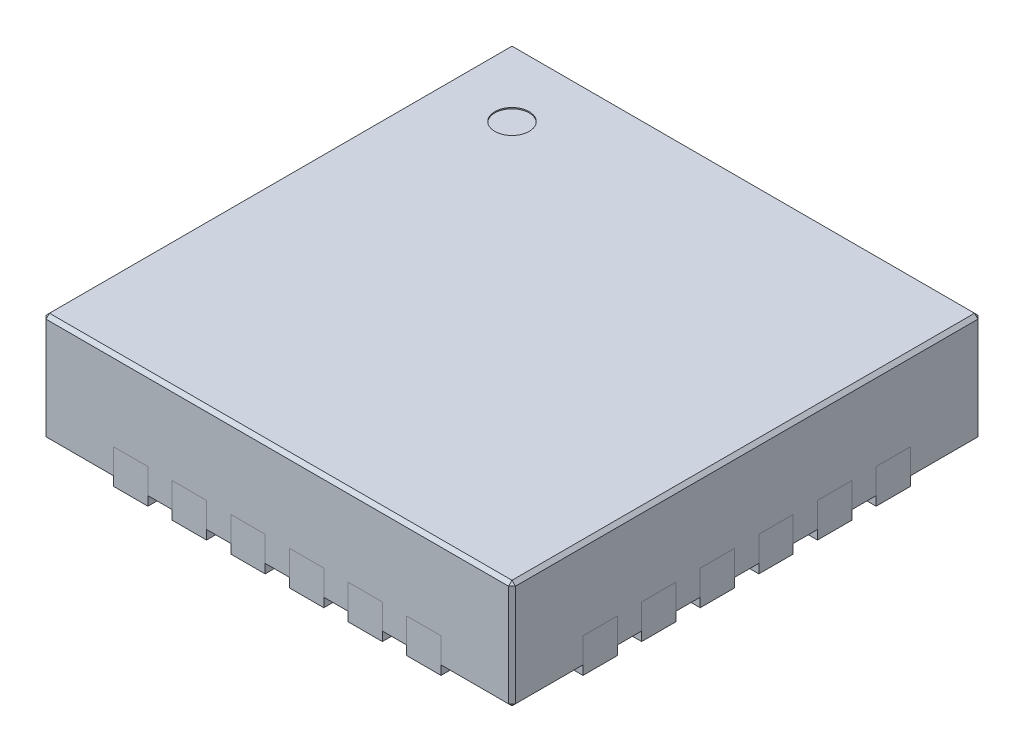
SolidWorks part; units mm, degrees
ref_plane "Front" through (0, 0, 0) normal (0, 0, 1) x (1, 0, 0)
ref_plane "Top" through (0, 0, 0) normal (0, 1, 0) x (1, 0, 0)
ref_plane "Right" through (0, 0, 0) normal (1, 0, 0) x (0, 0, -1)
sketch "Эскиз1" plane through (0, 0, 0) normal (0, 1, 0) x (1, 0, 0)
  line L0 (-2.05, -1.43) -> (-1.65, -1.43)
  line L1 (-2.05, 2.05) -> (2.05, 2.05)
  line L2 (-2.05, 2.05) -> (-2.05, -2.05)
  line L3 (-2.05, -2.05) -> (2.05, -2.05)
  line L4 (2.05, 2.05) -> (2.05, -2.05)
  line L5 (-2.05, 2.05) -> (2.05, -2.05) construction
  line L6 (-2.05, -2.05) -> (2.05, 2.05) construction
  line L7 (-1.65, -1.43) -> (-1.65, -1.13)
  line L8 (-1.65, -1.13) -> (-2.05, -1.13)
  line L9 (-2.05, 1.13) -> (-1.65, 1.13)
  line L10 (-1.65, 1.13) -> (-1.65, 1.43)
  line L11 (-1.65, 1.43) -> (-2.05, 1.43)
  line L12 (-2.05, 0.918) -> (-1.65, 0.918)
  line L13 (-1.65, 0.918) -> (-1.65, 0.618)
  line L14 (-1.65, 0.618) -> (-2.05, 0.618)
  line L15 (-2.05, 0.406) -> (-1.65, 0.406)
  line L16 (-1.65, 0.406) -> (-1.65, 0.106)
  line L17 (-1.65, 0.106) -> (-2.05, 0.106)
  line L18 (-2.05, -0.106) -> (-1.65, -0.106)
  line L19 (-1.65, -0.106) -> (-1.65, -0.406)
  line L20 (-1.65, -0.406) -> (-2.05, -0.406)
  line L21 (-2.05, -0.618) -> (-1.65, -0.618)
  line L22 (-1.65, -0.618) -> (-1.65, -0.918)
  line L23 (-1.65, -0.918) -> (-2.05, -0.918)
  line L24 (0, -1.28) -> (0, 1.28) construction
  line L25 (0, 1.28) -> (-1.65, 1.28) construction
  line L26 (0, -1.28) -> (-1.65, -1.28) construction
  line L27 (-1.65, -1.28) -> (-1.85, -1.43)
  line L28 (-1.65, 1.28) -> (-1.85, 1.43)
  line L29 (-1.28, 1.65) -> (-1.43, 1.85)
  line L30 (1.28, 1.65) -> (1.43, 1.85)
  line L31 (0.918, 1.65) -> (0.918, 2.05)
  line L32 (0.618, 1.65) -> (0.918, 1.65)
  line L33 (0.618, 2.05) -> (0.618, 1.65)
  line L34 (0.406, 1.65) -> (0.406, 2.05)
  line L35 (0.106, 1.65) -> (0.406, 1.65)
  line L36 (0.106, 2.05) -> (0.106, 1.65)
  line L37 (-0.106, 1.65) -> (-0.106, 2.05)
  line L38 (-0.406, 1.65) -> (-0.106, 1.65)
  line L39 (-0.406, 2.05) -> (-0.406, 1.65)
  line L40 (-0.618, 1.65) -> (-0.618, 2.05)
  line L41 (-0.918, 1.65) -> (-0.618, 1.65)
  line L42 (-0.918, 2.05) -> (-0.918, 1.65)
  line L43 (-1.43, 1.65) -> (-1.43, 2.05)
  line L44 (-1.13, 1.65) -> (-1.43, 1.65)
  line L45 (-1.13, 2.05) -> (-1.13, 1.65)
  line L46 (1.13, 1.65) -> (1.13, 2.05)
  line L47 (1.43, 1.65) -> (1.13, 1.65)
  line L48 (1.43, 2.05) -> (1.43, 1.65)
  line L49 (1.28, -1.65) -> (1.43, -1.85)
  line L50 (-1.28, -1.65) -> (-1.43, -1.85)
  line L51 (-0.918, -1.65) -> (-0.918, -2.05)
  line L52 (-0.618, -1.65) -> (-0.918, -1.65)
  line L53 (-0.618, -2.05) -> (-0.618, -1.65)
  line L54 (-0.406, -1.65) -> (-0.406, -2.05)
  line L55 (-0.106, -1.65) -> (-0.406, -1.65)
  line L56 (-0.106, -2.05) -> (-0.106, -1.65)
  line L57 (0.106, -1.65) -> (0.106, -2.05)
  line L58 (0.406, -1.65) -> (0.106, -1.65)
  line L59 (0.406, -2.05) -> (0.406, -1.65)
  line L60 (0.618, -1.65) -> (0.618, -2.05)
  line L61 (0.918, -1.65) -> (0.618, -1.65)
  line L62 (0.918, -2.05) -> (0.918, -1.65)
  line L63 (1.43, -1.65) -> (1.43, -2.05)
  line L64 (1.13, -1.65) -> (1.43, -1.65)
  line L65 (1.13, -2.05) -> (1.13, -1.65)
  line L66 (-1.13, -1.65) -> (-1.13, -2.05)
  line L67 (-1.43, -1.65) -> (-1.13, -1.65)
  line L68 (-1.43, -2.05) -> (-1.43, -1.65)
  line L69 (1.65, 1.28) -> (1.85, 1.43)
  line L70 (1.65, -1.28) -> (1.85, -1.43)
  line L71 (1.65, -0.918) -> (2.05, -0.918)
  line L72 (1.65, -0.618) -> (1.65, -0.918)
  line L73 (2.05, -0.618) -> (1.65, -0.618)
  line L74 (1.65, -0.406) -> (2.05, -0.406)
  line L75 (1.65, -0.106) -> (1.65, -0.406)
  line L76 (2.05, -0.106) -> (1.65, -0.106)
  line L77 (1.65, 0.106) -> (2.05, 0.106)
  line L78 (1.65, 0.406) -> (1.65, 0.106)
  line L79 (2.05, 0.406) -> (1.65, 0.406)
  line L80 (1.65, 0.618) -> (2.05, 0.618)
  line L81 (1.65, 0.918) -> (1.65, 0.618)
  line L82 (2.05, 0.918) -> (1.65, 0.918)
  line L83 (1.65, 1.43) -> (2.05, 1.43)
  line L84 (1.65, 1.13) -> (1.65, 1.43)
  line L85 (2.05, 1.13) -> (1.65, 1.13)
  line L86 (1.65, -1.13) -> (2.05, -1.13)
  line L87 (1.65, -1.43) -> (1.65, -1.13)
  line L88 (2.05, -1.43) -> (1.65, -1.43)
  line L89 (-1.475, 0.9093) -> (-0.9093, 1.475)
  line L90 (-1.475, 1.475) -> (1.475, 1.475)
  line L91 (-1.475, 1.475) -> (-1.475, -1.475)
  line L92 (-1.475, -1.475) -> (1.475, -1.475)
  line L93 (1.475, 1.475) -> (1.475, -1.475)
  line L94 (-1.475, 1.475) -> (1.475, -1.475) construction
  line L95 (-1.475, -1.475) -> (1.475, 1.475) construction
  point P0 (0, 0)
  point P8 (-1.65, 0.768)
  point P13 (-1.65, 0.256)
  point P34 (-1.65, -0.256)
  point P37 (-1.65, -0.768)
  point P68 (0.768, 1.65)
  point P69 (0.256, 1.65)
  point P70 (-0.256, 1.65)
  point P71 (-0.768, 1.65)
  point P100 (-0.768, -1.65)
  point P101 (-0.256, -1.65)
  point P102 (0.256, -1.65)
  point P103 (0.768, -1.65)
  point P132 (1.65, -0.768)
  point P133 (1.65, -0.256)
  point P134 (1.65, 0.256)
  point P135 (1.65, 0.768)
  point P136 (0, 0)
  dimension "D1" = 4.1
  dimension "D2" = 0.3
  dimension "D3" = 0.4
  dimension "D4" = 0.512
  dimension "D6" = 0.512
  dimension "D5" = 2.56
  dimension "D7" = 0.512
  dimension "D8" = 0.512
  dimension "D9" = 0.512
  dimension "D10" = 2.95
  dimension "D11" = 45
  dimension "D12" = 0.4
extrude "Бобышка-Вытянуть1" add sketch "Эскиз1" along normal blind 0.3 contours L45 L1 L43 L29 L44 | L1 L42 L41 L40 | L1 L39 L38 L37 | L1 L36 L35 L34 | L1 L33 L32 L31 | L48 L1 L46 L47 L30 | L85 L4 L83 L69 L84 | L4 L82 L81 L80 | L4 L79 L78 L77 | L4 L76 L75 L74 | L4 L73 L72 L71 | L88 L4 L86 L87 L70 | L65 L3 L63 L49 L64 | L3 L62 L61 L60 | L3 L59 L58 L57 | L3 L56 L55 L54 | L3 L53 L52 L51 | L68 L3 L66 L67 L50 | L27 L7 L8 L2 L0 | L23 L22 L21 L2 | L20 L19 L18 L2 | L17 L16 L15 L2 | L14 L13 L12 L2 | L10 L28 L11 L2 L9 | L93 L90 L89 L91 L92 region at (-1.869, 0, 1.2657) region at (-1.85, 0, 0.768) region at (-1.2657, 0, 1.869) region at (-1.85, 0, 0.256) region at (-0.768, 0, 1.85) region at (-1.85, 0, -0.256) region at (-0.256, 0, 1.85) region at (-1.85, 0, -0.768) region at (0.256, 0, 1.85) region at (-1.869, 0, -1.2657) region at (0.768, 0, 1.85) region at (1.2657, 0, 1.869) region at (-1.2657, 0, -1.869) region at (-0.768, 0, -1.85) region at (1.869, 0, 1.2657) region at (-0.256, 0, -1.85) region at (1.85, 0, 0.768) region at (0.256, 0, -1.85) region at (1.85, 0, 0.256) region at (0.768, 0, -1.85) region at (1.85, 0, -0.256) region at (1.2657, 0, -1.869) region at (1.85, 0, -0.768) region at (1.869, 0, -1.2657) region at (0.0241, 0, 0.0241)
extrude "Бобышка-Вытянуть2" add sketch "Эскиз1<3>" along normal blind 0.25 from offset 0.05 separate body contours L4 L88 L87 L86 L71 L72 L73 L74 L75 L76 L77 L78 L79 L80 L81 L82 L85 L84 L83 L1 L48 L47 L46 L31 L32 L33 L34 L35 L36 L37 L38 L39 L40 L41 L42 | L44 L29 L43 | L28 L10 L11 | L48 L30 L47 | L84 L69 L83 | L88 L70 L87 | L64 L49 L63 | L68 L50 L67 | L7 L27 L0 | L90 L91 L89 region at (-1.95, 0, 1.488) region at (-1.7167, 0, 1.38) region at (-1.38, 0, 1.7167) region at (-1.7167, 0, -1.38) region at (-1.38, 0, -1.7167) region at (1.38, 0, 1.7167) region at (1.7167, 0, 1.38) region at (1.38, 0, -1.7167) region at (1.7167, 0, -1.38) region at (-1.2864, 0, -1.2864)
sketch "Эскиз1<3>" plane through (0, 0, 0) normal (0, 1, 0) x (1, 0, 0) same geometry as "Эскиз1"
extrude "Бобышка-Вытянуть3" add sketch "Эскиз1<5>" along normal blind 0.7 from offset 0.3 contours L4 L88 L87 L86 L71 L72 L73 L74 L75 L76 L77 L78 L79 L80 L81 L82 L85 L84 L83 L1 L48 L47 L46 L31 L32 L33 L34 L35 L36 L37 L38 L39 L40 L41 L42 | L68 L3 L66 L67 L50 | L68 L50 L67 | L3 L53 L52 L51 | L3 L56 L55 L54 | L3 L59 L58 L57 | L3 L62 L61 L60 | L65 L3 L63 L49 L64 | L64 L49 L63 | L88 L4 L86 L87 L70 | L88 L70 L87 | L4 L73 L72 L71 | L4 L76 L75 L74 | L4 L79 L78 L77 | L4 L82 L81 L80 | L85 L4 L83 L69 L84 | L84 L69 L83 | L48 L1 L46 L47 L30 | L48 L30 L47 | L1 L33 L32 L31 | L1 L36 L35 L34 | L1 L39 L38 L37 | L1 L42 L41 L40 | L45 L1 L43 L29 L44 | L44 L29 L43 | L10 L28 L11 L2 L9 | L28 L10 L11 | L14 L13 L12 L2 | L17 L16 L15 L2 | L20 L19 L18 L2 | L23 L22 L21 L2 | L27 L7 L8 L2 L0 | L7 L27 L0 | L93 L90 L89 L91 L92 | L90 L91 L89 region at (-1.869, 0, 1.2657) region at (-1.95, 0, 1.488) region at (-1.7167, 0, 1.38) region at (-1.85, 0, 0.768) region at (-1.2657, 0, 1.869) region at (-1.38, 0, 1.7167) region at (-1.85, 0, 0.256) region at (-0.768, 0, 1.85) region at (-1.85, 0, -0.256) region at (-0.256, 0, 1.85) region at (-1.85, 0, -0.768) region at (0.256, 0, 1.85) region at (-1.869, 0, -1.2657) region at (0.768, 0, 1.85) region at (-1.7167, 0, -1.38) region at (1.2657, 0, 1.869) region at (-1.2657, 0, -1.869) region at (-1.38, 0, -1.7167) region at (1.38, 0, 1.7167) region at (-0.768, 0, -1.85) region at (1.869, 0, 1.2657) region at (1.7167, 0, 1.38) region at (-0.256, 0, -1.85) region at (1.85, 0, 0.768) region at (0.256, 0, -1.85) region at (1.85, 0, 0.256) region at (0.768, 0, -1.85) region at (1.85, 0, -0.256) region at (1.2657, 0, -1.869) region at (1.85, 0, -0.768) region at (1.38, 0, -1.7167) region at (1.869, 0, -1.2657) region at (1.7167, 0, -1.38) region at (-1.2864, 0, -1.2864) region at (0.0241, 0, 0.0241)
sketch "Эскиз1<5>" plane through (0, 0, 0) normal (0, 1, 0) x (1, 0, 0) same geometry as "Эскиз1"
sketch "Эскиз2" plane through (0, 1, 0) normal (0, 1, 0) x (1, 0, 0)
  line L0 (-2.05, 2.05) -> (2.05, 2.05) construction
  line L1 (-2.05, 2.05) -> (-2.05, -2.05) construction
  circle A0 centre (-1.45, 1.45) radius 0.15
  dimension "D1" = 0.3
  dimension "D2" = 0.6
  dimension "D3" = 0.6
extrude "Вырез-Вытянуть1" cut sketch "Эскиз2" against normal blind 0.01
chamfer "Фаска1" distance 0.03 angle 45 36 edges at (1.024, 0.05, 2.05) (0.512, 0.05, 2.05) (0, 0.05, 2.05) (-0.512, 0.05, 2.05) (-1.024, 0.05, 2.05) (-2.05, 0.05, 1.024) (-2.05, 0.05, 0.512) (-2.05, 0.05, 0) (-2.05, 0.05, -0.512) (-2.05, 0.05, -1.024) (-1.024, 0.05, -2.05) (-0.512, 0.05, -2.05) (0, 0.05, -2.05) (0.512, 0.05, -2.05) (1.024, 0.05, -2.05) (2.05, 0.05, -1.024) (2.05, 0.05, -0.512) (2.05, 0.05, 0) (2.05, 0.05, 0.512) (2.05, 0.05, 1.024) (1.74, 0.05, 2.05) (-1.74, 0.05, 2.05) (-2.05, 0.05, 1.74) (-2.05, 0.05, -1.74) (-1.74, 0.05, -2.05) (1.74, 0.05, -2.05) (2.05, 0.05, -1.74) (2.05, 0.05, 1.74) (2.05, 0.525, -2.05) (2.05, 0.525, 2.05) (-2.05, 0.525, 2.05) (-2.05, 0.525, -2.05) (0, 1, -2.05) (2.05, 1, 0) (0, 1, 2.05) (-2.05, 1, 0)
